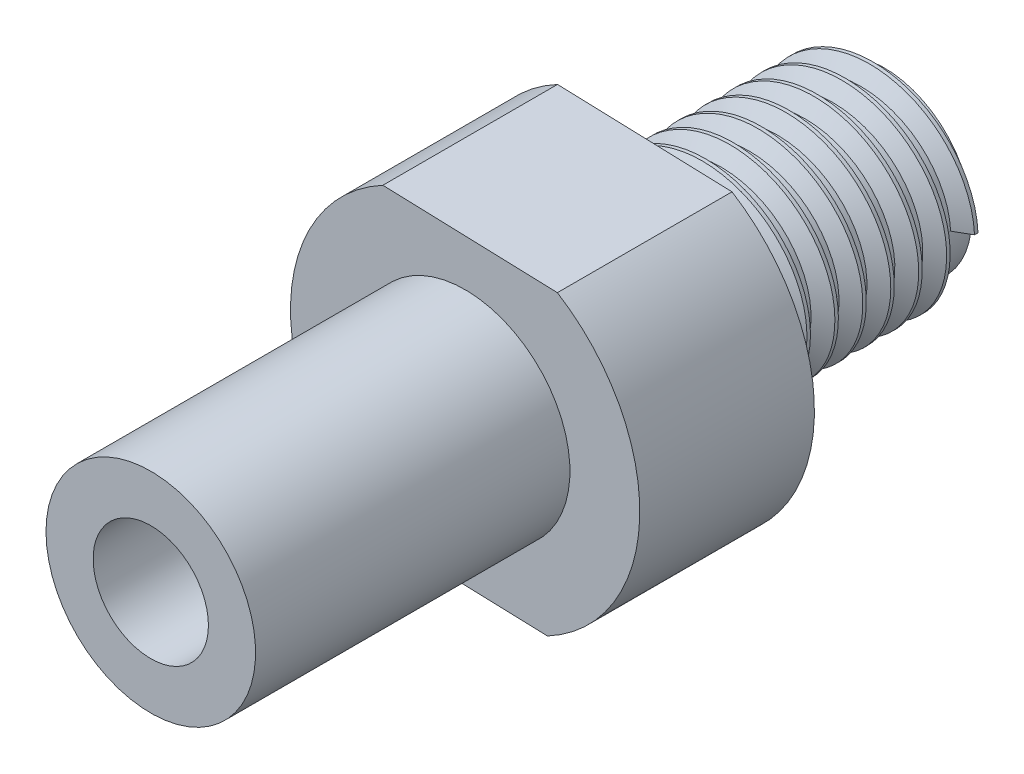
SolidWorks part; units mm, degrees
material "Stainless Steel (ferritic)"
ref_plane "Front Plane" through (0, 0, 0) normal (0, 0, 1) x (1, 0, 0)
ref_plane "Top Plane" through (0, 0, 0) normal (0, 1, 0) x (1, 0, 0)
ref_plane "Right Plane" through (0, 0, 0) normal (1, 0, 0) x (0, 0, -1)
sketch "Sketch1" plane through (0, 0, 0) normal (0, 0, 1) x (1, 0, 0)
  circle A0 centre (0, 0) radius 2.5
  dimension "D1" = 5
extrude "Boss-Extrude1" add sketch "Sketch1" along normal blind 7
thread "Thread1" pitch 0.8 method extrude profile "Thread Profile1" start angle 0, offset 0, length 6, pitch 0.8, diameter 5
ref_plane "Plane1" through (2.5, 0, 0) normal (0, -1, 0) x (1, 0, 0)
sketch "Thread Profile1" plane through (2.5, 0, 0) normal (0, -1, 0) x (1, 0, 0)
  line L0 (0, 0) -> (0, 0.8) construction
  line L1 (0, 0) -> (0.433, 0.25)
  line L2 (0.433, 0.25) -> (0.433, 0.35)
  line L3 (0.433, 0.35) -> (0, 0.6)
  line L4 (0.433, 0.3) -> (0, 0.3) construction
  line L11 (0, 0) -> (0, 0.6)
  point P2 (0, 0)
  dimension "Pitch" = 0.8
  dimension "Profile_Angle" = 60
  dimension "Profile_Land" = 0.1
  dimension "Profile_Height" = 0.433
sketch "Sketch4" plane through (0, 0, 7) normal (0, 0, 1) x (1, 0, 0)
  circle A0 centre (0, 0) radius 5
  dimension "D1" = 10
extrude "Boss-Extrude2" add sketch "Sketch4" along normal blind 5
sketch "Sketch11" plane through (0, 0, 12) normal (0, 0, 1) x (1, 0, 0)
  circle A0 centre (0, 0) radius 3
extrude "Boss-Extrude3" add sketch "Sketch11" along normal blind 9
hole_wizard "M4x0.7 Tapped Hole1" positions "Sketch12" profile "Sketch13" tap size "M4x0.7" standard "ANSI Metric"
sketch "Sketch12" plane through (0, 0, 21) normal (0, 0, 1) x (1, 0, 0)
  point P0 (0, 0)
sketch "Sketch13" plane through (0, 0, 21) normal (1, 0, 0) x (0, -1, 0)
  line L0 (0, 0) -> (0, 6.9914)
  line L1 (0, 6.9914) -> (1.65, 6)
  line L2 (1.65, 6) -> (1.65, 0)
  line L5 (1.65, 0) -> (0, 0)
  line L10 (0, 6.9914) -> (-1.65, 6) construction
  line L11 (0, -6.35) -> (0, 107.95) construction
  dimension "Tap Drill Dia." = 3.3
  dimension "Tap Drill Depth" = 6
  dimension "Drill Angle" = 118
cosmetic thread "Hole Thread1" parameters "D1"=5, "D2"=4
sketch "Sketch14" plane through (0, 0, 12) normal (0, 0, 1) x (1, 0, 0)
  line L1 (2.6409, 4.2456) -> (-2.3564, 4.4099)
  line L2 (-2.3564, 4.4099) -> (-4.9973, 0.1643)
  line L3 (-4.9973, 0.1643) -> (-2.6409, -4.2456)
  line L4 (-2.6409, -4.2456) -> (2.3564, -4.4099)
  line L5 (2.3564, -4.4099) -> (4.9973, -0.1643)
  line L6 (4.9973, -0.1643) -> (2.6409, 4.2456)
  circle A0 centre (0, 0) radius 4.3301 construction
  circle A1 centre (0, 0) radius 5
  circle M3 centre (0, 0) radius 5
extrude "Cut-Extrude2" cut sketch "Sketch14" against normal blind 9 contours L1 M3 | L4 M3 region at (0.1511, 4.5972, 12) region at (-0.1511, -4.5972, 12)
